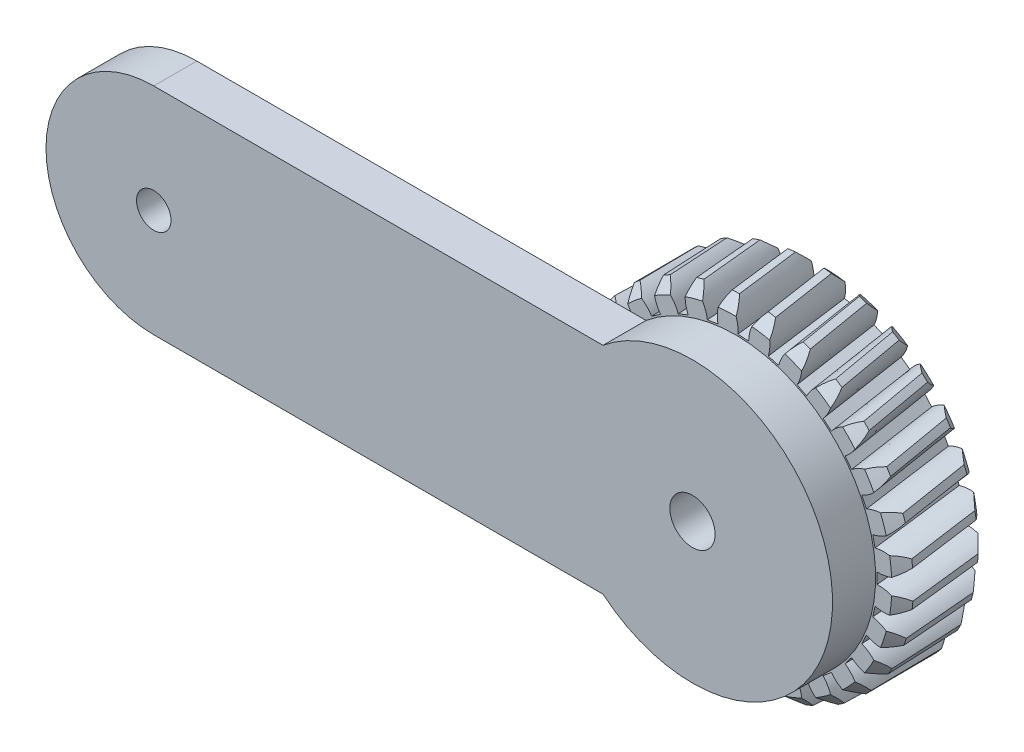
SolidWorks part; units mm, degrees
ref_plane "Front Plane" through (0, 0, 0) normal (1, 0, 0) x (0, 1, 0)
ref_plane "Top Plane" through (0, 0, 0) normal (0, 0, 1) x (0, 1, 0)
ref_plane "Right Plane" through (0, 0, 0) normal (0, 1, 0) x (-1, 0, 0)
sketch "Sketch5" plane through (0, 0, 0) normal (0, 0, 1) x (0, 1, 0)
  circle A0 centre (0, 0) radius 15.5
  dimension "D1" = 31
extrude "Boss-Extrude1" add sketch "Sketch5" along normal blind 8
chamfer "Chamfer1" distance 1 angle 45 2 edges at (15.5, 0, 8) (15.5, 0, 0)
sketch "Sketch9" plane through (0, 0, 8) normal (0, 0, 1) x (1, 0, 0)
  circle A0 centre (0, 0) radius 15.5 construction
  circle A1 centre (0, 0) radius 15.5
curve "Helix/Spiral1" pitch 704.2254 height 20 radius 15.5 left hand yes centre (0, 0, 8) axis (0, 0, -1) start towards (-1, 0, 0)
sketch "Sketch10" plane through (0, 0, 8) normal (0, 0, 1) x (1, 0, 0)
  line L0 (0, 0) -> (31, 0) construction
  line L1 (13.1433, 0.5) -> (13.1433, -0.5)
  circle A0 centre (0, 0) radius 15.5 construction
  arc A1 (15.4433, -1.325) -> (15.4433, 1.325) centre (0, 0) ccw
  arc A2 (13.1433, 0.5) -> (15.4433, 1.325) centre (13.2582, 3.798) ccw
  arc A3 (13.1433, -0.5) -> (15.4433, -1.325) centre (13.2582, -3.798) cw
  point P9 (13.1433, 0)
  dimension "D2" = 2.65
  dimension "D4" = 3.3
  dimension "D1" = 1
  dimension "D3" = 2.3
sweep "Cut-Sweep1" cut profiles "Sketch10" path "Helix/Spiral1" align with end faces yes
pattern_circular "CirPattern1" count 29 over 360 about axis through (0, 0, 8) along (0, 0, -1) of "Cut-Sweep1" reverse direction yes
sketch "Sketch12" plane through (0, 0, 0) normal (0, 0, 1) x (0, 1, 0)
  line L0 (0, 0) -> (0, 50) construction
  line L1 (0, 25) -> (-14.1559, 25) construction
  line L2 (10, 50) -> (10, 8.3066)
  line L3 (-10, 50) -> (-10, 8.3066)
  line L4 (-10, 8.3066) -> (10, 8.3066) construction
  arc A0 (-10, 8.3066) -> (10, 8.3066) centre (0, 0) ccw
  arc A1 (10, 50) -> (-10, 50) centre (0, 50) ccw
  circle A3 centre (0, 50) radius 1.6
  dimension "D1" = 26
  dimension "D2" = 20
  dimension "D4" = 3.2
  dimension "D3" = 50
extrude "Boss-Extrude2" add sketch "Sketch12" along normal blind 4 from surface starting at face at (0, 0, 8)
sketch "Sketch11" plane through (0, 0, 0) normal (0, 0, 1) x (0, 1, 0)
  circle A0 centre (0, 0) radius 2.1
  dimension "D1" = 4.2
extrude "Cut-Extrude1" cut sketch "Sketch11" along normal blind 15
